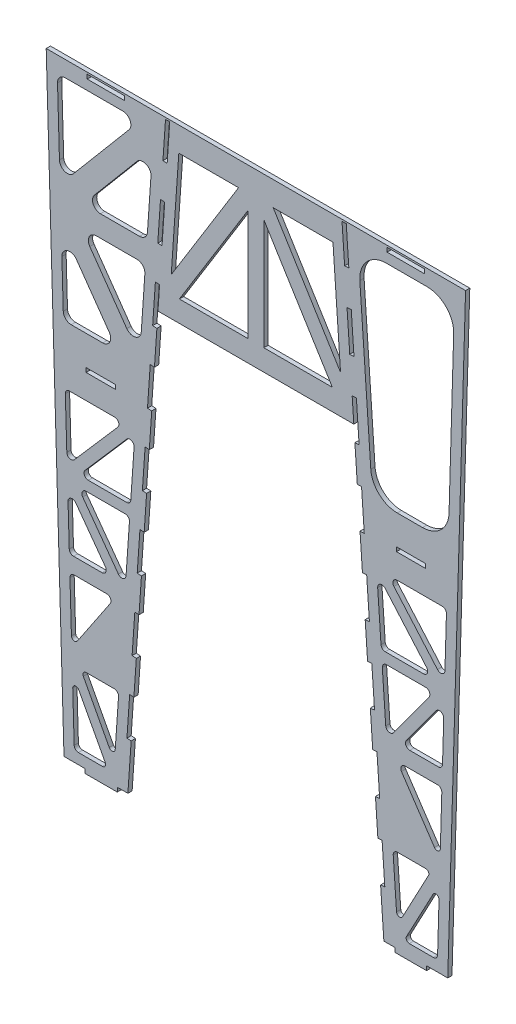
SolidWorks part; units mm, degrees
ref_plane "Front Plane" through (0, 0, 0) normal (0, 0, 1) x (1, 0, 0)
ref_plane "Top Plane" through (0, 0, 0) normal (0, 1, 0) x (1, 0, 0)
ref_plane "Right Plane" through (0, 0, 0) normal (1, 0, 0) x (0, 0, -1)
sketch "Sketch1" plane through (0, 0, 0) normal (0, 0, 1) x (1, 0, 0)
  line L0 (-288.2759, 0) -> (288.2759, 0) construction
  line L1 (-215.8925, 1465.1633) -> (215.8925, 1465.1633)
  line L2 (0, 0) -> (0, 1733.4513) construction
  line L3 (19.05, 1104.9) -> (205.6376, 1104.9)
  line L4 (202.8026, 1145.716) -> (41.4459, 1406.7433)
  line L5 (205.6376, 1104.9) -> (19.05, 1406.7433) construction
  line L6 (205.6376, 1104.9) -> (184.6725, 1406.7433)
  line L7 (183.2417, 1104.9) -> (15.2162, 1376.7154)
  line L8 (19.05, 1406.7433) -> (19.05, 1104.9)
  line L9 (184.6725, 1406.7433) -> (19.05, 1406.7433)
  line L10 (306.6278, 17.4764) -> (234.6272, 1054.1)
  line L12 (459.7218, 17.4764) -> (502.3797, 1465.1633)
  line L13 (459.4357, 7.4824) -> (519.9157, 2060.3987) construction
  line L15 (266.6925, 1465.1633) -> (368.5375, 1465.1633)
  line L16 (-237.2124, 1016.8799) -> (-230.6925, 1110.7494) construction
  line L18 (237.2124, 1016.8799) -> (230.6925, 1110.7494) construction
  line L19 (-408.9218, 7.3164) -> (-332.1008, 7.3164)
  line L20 (-502.3797, 1465.1633) -> (-215.8925, 1465.1633)
  line L22 (408.9218, 7.3164) -> (332.7218, 7.3164)
  line L24 (-408.9218, 17.4764) -> (-408.9218, 7.3164) construction
  line L30 (-408.9218, 17.4764) -> (-408.9218, 7.3164)
  line L31 (502.3797, 1465.1633) -> (368.5375, 1465.1633)
  line L32 (-332.1008, 17.4764) -> (-332.1008, 7.3164) construction
  line L33 (-332.1008, 17.4764) -> (-332.1008, 7.3164)
  line L34 (408.9218, 17.4764) -> (408.9218, 7.3164) construction
  line L35 (408.9218, 17.4764) -> (408.9218, 7.3164)
  line L40 (332.7218, 17.4764) -> (332.7218, 7.3164) construction
  line L43 (332.7218, 17.4764) -> (332.7218, 7.3164)
  line L44 (459.7218, 17.4764) -> (408.9218, 17.4764) construction
  line L45 (459.7218, 17.4764) -> (408.9218, 17.4764)
  line L49 (-408.9218, 17.4764) -> (-459.7218, 17.4764)
  line L52 (-332.1008, 17.4764) -> (-306.6278, 17.4764)
  line L53 (332.7218, 17.4764) -> (306.6278, 17.4764)
  line L55 (-459.7218, 17.4764) -> (-502.3797, 1465.1633)
  line L56 (-459.4357, 7.4824) -> (-519.9157, 2060.3987) construction
  line L81 (215.8925, 1465.1633) -> (266.6925, 1465.1633)
  line L90 (234.6272, 1054.1) -> (-234.6272, 1054.1)
  line L100 (-234.6272, 1054.1) -> (-306.6278, 17.4764)
  line L124 (-184.6725, 1406.7433) -> (-19.05, 1406.7433)
  line L125 (-19.05, 1406.7433) -> (-19.05, 1104.9)
  line L126 (-183.2417, 1104.9) -> (-15.2162, 1376.7154)
  line L127 (-205.6376, 1104.9) -> (-19.05, 1406.7433) construction
  line L128 (-202.8026, 1145.716) -> (-41.4459, 1406.7433)
  line L129 (-205.6376, 1104.9) -> (-184.6725, 1406.7433)
  line L130 (-19.05, 1104.9) -> (-205.6376, 1104.9)
  point P0 (0, 0)
  point P3 (0, 0)
  point P106 (0, 0)
  point P118 (0, 1054.1)
  dimension "D6" = 25.4
  dimension "D7" = 50.8
  dimension "D8" = 58.42
  dimension "D9" = 19.05
  dimension "D19" = 288.2759
  dimension "D22" = 19.05
  dimension "D23" = 19.05
  dimension "D24" = 1054.1
  dimension "D49" = 50.8
extrude "Boss-Extrude1" add sketch "Sketch1" along normal blind 10.16 contours L20 | L100 L90 L125 L130 L129 L124 | L100 | L130 L126 L125 L124 L128 L129 | L81 | L4 L9 L8 L7 L3 L6 | L15 region at (0, 1447.4578, 0) region at (111.9691, 1256.3298, 0) region at (-111.9691, 1256.3298, 0)
fillet "Fillet1" [suppressed] radius 19.05
sketch "Sketch2" plane through (0, 0, 0) normal (0, 0, 1) x (1, 0, 0)
  line L18 (-222.6942, 1372.2749) -> (-212.5765, 1371.5721) construction
  line L56 (-216.5353, 1460.9479) -> (-222.6942, 1372.2749) construction
  line L57 (-212.5765, 1371.5721) -> (-206.3688, 1460.9479) construction
  line L58 (-206.3688, 1460.9479) -> (-216.5353, 1460.9479) construction
  line L59 (-222.6942, 1372.2749) -> (-212.5765, 1371.5721)
  line L61 (-216.5353, 1460.9479) -> (-222.6942, 1372.2749)
  line L63 (-212.5765, 1371.5721) -> (-206.3688, 1460.9479)
  line L176 (-206.3688, 1460.9479) -> (-216.5353, 1460.9479)
  line L181 (-224.8945, 1194.226) -> (-235.0121, 1194.9287) construction
  line L194 (-224.8945, 1194.226) -> (-218.3727, 1288.1221) construction
  line L199 (-218.3727, 1288.1221) -> (-228.4904, 1288.8248) construction
  line L208 (-228.4904, 1288.8248) -> (-235.0121, 1194.9287) construction
  line L213 (-224.8945, 1194.226) -> (-235.0121, 1194.9287)
  line L330 (-224.8945, 1194.226) -> (-218.3727, 1288.1221)
  line L331 (-218.3727, 1288.1221) -> (-228.4904, 1288.8248)
  line L332 (-228.4904, 1288.8248) -> (-235.0121, 1194.9287)
  line L333 (224.8945, 1194.226) -> (235.0121, 1194.9287) construction
  line L334 (235.0121, 1194.9287) -> (228.4904, 1288.8248) construction
  line L335 (218.3727, 1288.1221) -> (224.8945, 1194.226) construction
  line L336 (228.4904, 1288.8248) -> (218.3727, 1288.1221) construction
  line L337 (212.5765, 1371.5721) -> (222.6942, 1372.2749) construction
  line L338 (206.3688, 1460.9479) -> (212.5765, 1371.5721) construction
  line L339 (216.5353, 1460.9479) -> (206.3688, 1460.9479) construction
  line L340 (222.6942, 1372.2749) -> (216.5353, 1460.9479) construction
  line L341 (224.8945, 1194.226) -> (235.0121, 1194.9287)
  line L342 (235.0121, 1194.9287) -> (228.4904, 1288.8248)
  line L343 (218.3727, 1288.1221) -> (224.8945, 1194.226)
  line L344 (228.4904, 1288.8248) -> (218.3727, 1288.1221)
  line L345 (212.5765, 1371.5721) -> (222.6942, 1372.2749)
  line L346 (206.3688, 1460.9479) -> (212.5765, 1371.5721)
  line L347 (216.5353, 1460.9479) -> (206.3688, 1460.9479)
  line L348 (222.6942, 1372.2749) -> (216.5353, 1460.9479)
  line L349 (-240.8102, 1111.4521) -> (-247.33, 1017.5826) construction
  line L350 (-247.33, 1017.5826) -> (-237.2124, 1016.8799) construction
  line L351 (-230.6925, 1110.7494) -> (-240.8102, 1111.4521) construction
  line L353 (-240.8102, 1111.4521) -> (-247.33, 1017.5826)
  line L354 (-247.33, 1017.5826) -> (-237.2124, 1016.8799)
  line L355 (-230.6925, 1110.7494) -> (-240.8102, 1111.4521)
  line L357 (237.2124, 1016.8799) -> (247.33, 1017.5826) construction
  line L358 (247.33, 1017.5826) -> (240.8102, 1111.4521) construction
  line L360 (240.8102, 1111.4521) -> (230.6925, 1110.7494) construction
  line L361 (237.2124, 1016.8799) -> (247.33, 1017.5826)
  line L362 (247.33, 1017.5826) -> (240.8102, 1111.4521)
  line L364 (240.8102, 1111.4521) -> (230.6925, 1110.7494)
  line L365 (-306.6278, 17.4764) -> (-234.6272, 1054.1)
  line L366 (-234.6272, 1054.1) -> (234.6272, 1054.1)
  line L367 (234.6272, 1054.1) -> (306.6278, 17.4764)
  line L372 (408.9218, 17.4764) -> (459.7218, 17.4764)
  line L373 (459.7218, 17.4764) -> (502.3797, 1465.1633)
  line L374 (502.3797, 1465.1633) -> (-502.3797, 1465.1633)
  line L375 (-502.3797, 1465.1633) -> (-459.7218, 17.4764)
  line L376 (-459.7218, 17.4764) -> (-408.9218, 17.4764)
  line L377 (-408.9218, 17.4764) -> (-408.9218, 7.3164)
  line L378 (-408.9218, 7.3164) -> (-332.1008, 7.3164)
  line L379 (-332.1008, 7.3164) -> (-332.1008, 17.4764)
  line L380 (-332.1008, 17.4764) -> (-306.6278, 17.4764)
  line L381 (-298.8019, 130.1492) -> (-292.2913, 223.886)
  line L405 (-243.0122, 933.3767) -> (-253.1299, 934.0795) construction
  line L406 (-253.1299, 934.0795) -> (-259.648, 840.2365) construction
  line L407 (-249.5303, 839.5337) -> (-259.648, 840.2365) construction
  line L408 (-243.0122, 933.3767) -> (-253.1299, 934.0795)
  line L417 (-253.1299, 934.0795) -> (-259.648, 840.2365)
  line L418 (-249.5303, 839.5337) -> (-259.648, 840.2365)
  line L419 (243.0122, 933.3767) -> (253.1299, 934.0795) construction
  line L420 (253.1299, 934.0795) -> (259.648, 840.2365) construction
  line L421 (249.5303, 839.5337) -> (259.648, 840.2365) construction
  line L422 (243.0122, 933.3767) -> (253.1299, 934.0795)
  line L423 (253.1299, 934.0795) -> (259.648, 840.2365)
  line L424 (249.5303, 839.5337) -> (259.648, 840.2365)
  line L425 (-267.6517, 578.6314) -> (-277.7694, 579.3341) construction
  line L426 (-255.332, 756.0041) -> (-265.4497, 756.7068) construction
  line L427 (-265.4497, 756.7068) -> (-271.9659, 662.8903) construction
  line L428 (-261.8482, 662.1876) -> (-271.9659, 662.8903) construction
  line L429 (-277.7694, 579.3341) -> (-284.2838, 485.5442) construction
  line L430 (-274.1661, 484.8415) -> (-284.2838, 485.5442) construction
  line L431 (-274.1661, 484.8415) -> (-284.2838, 485.5442)
  line L432 (-277.7694, 579.3341) -> (-284.2838, 485.5442)
  line L433 (-267.6517, 578.6314) -> (-277.7694, 579.3341)
  line L434 (-261.8482, 662.1876) -> (-271.9659, 662.8903)
  line L435 (-265.4497, 756.7068) -> (-271.9659, 662.8903)
  line L436 (-255.332, 756.0041) -> (-265.4497, 756.7068)
  line L437 (261.8482, 662.1876) -> (271.9659, 662.8903) construction
  line L438 (255.332, 756.0041) -> (265.4497, 756.7068) construction
  line L439 (265.4497, 756.7068) -> (271.9659, 662.8903) construction
  line L440 (261.8482, 662.1876) -> (271.9659, 662.8903)
  line L449 (255.332, 756.0041) -> (265.4497, 756.7068)
  line L450 (265.4497, 756.7068) -> (271.9659, 662.8903)
  line L451 (274.1661, 484.8415) -> (284.2838, 485.5442) construction
  line L452 (277.7694, 579.3341) -> (284.2838, 485.5442) construction
  line L453 (267.6517, 578.6314) -> (277.7694, 579.3341) construction
  line L454 (274.1661, 484.8415) -> (284.2838, 485.5442)
  line L455 (277.7694, 579.3341) -> (284.2838, 485.5442)
  line L456 (267.6517, 578.6314) -> (277.7694, 579.3341)
  line L457 (-298.8019, 130.1492) -> (-308.9196, 130.8519) construction
  line L458 (-302.4089, 224.5888) -> (-308.9196, 130.8519) construction
  line L459 (-292.2913, 223.886) -> (-302.4089, 224.5888) construction
  line L460 (-286.484, 307.4953) -> (-296.6017, 308.1981) construction
  line L461 (-290.0892, 401.9615) -> (-296.6017, 308.1981) construction
  line L462 (-279.9715, 401.2587) -> (-290.0892, 401.9615) construction
  line L463 (-298.8019, 130.1492) -> (-308.9196, 130.8519)
  line L464 (-302.4089, 224.5888) -> (-308.9196, 130.8519)
  line L465 (-292.2913, 223.886) -> (-302.4089, 224.5888)
  line L466 (-286.484, 307.4953) -> (-296.6017, 308.1981)
  line L467 (-290.0892, 401.9615) -> (-296.6017, 308.1981)
  line L468 (-279.9715, 401.2587) -> (-290.0892, 401.9615)
  line L469 (286.484, 307.4953) -> (296.6017, 308.1981) construction
  line L470 (279.9715, 401.2587) -> (290.0892, 401.9615) construction
  line L471 (290.0892, 401.9615) -> (296.6017, 308.1981) construction
  line L472 (286.484, 307.4953) -> (296.6017, 308.1981)
  line L473 (279.9715, 401.2587) -> (290.0892, 401.9615)
  line L474 (290.0892, 401.9615) -> (296.6017, 308.1981)
  line L475 (298.8019, 130.1492) -> (308.9196, 130.8519) construction
  line L476 (302.4089, 224.5888) -> (308.9196, 130.8519) construction
  line L477 (292.2913, 223.886) -> (302.4089, 224.5888) construction
  line L478 (298.8019, 130.1492) -> (308.9196, 130.8519)
  line L479 (302.4089, 224.5888) -> (308.9196, 130.8519)
  line L480 (292.2913, 223.886) -> (302.4089, 224.5888)
  line L481 (-230.6925, 1110.7494) -> (-237.2124, 1016.8799)
  line L482 (243.0122, 933.3767) -> (249.5303, 839.5337)
  line L483 (255.332, 756.0041) -> (261.8482, 662.1876)
  line L484 (-249.5303, 839.5337) -> (-243.0122, 933.3767)
  line L485 (-261.8482, 662.1876) -> (-255.332, 756.0041)
  line L486 (267.6517, 578.6314) -> (274.1661, 484.8415)
  line L487 (-286.484, 307.4953) -> (-279.9715, 401.2587)
  line L488 (-274.1661, 484.8415) -> (-267.6517, 578.6314)
  line L489 (279.9715, 401.2587) -> (286.484, 307.4953)
  line L490 (292.2913, 223.886) -> (298.8019, 130.1492)
  line L492 (230.6925, 1110.7494) -> (237.2124, 1016.8799)
  line L499 (306.6278, 17.4764) -> (332.7218, 17.4764)
  line L500 (332.7218, 17.4764) -> (332.7218, 7.3164)
  line L501 (332.7218, 7.3164) -> (408.9218, 7.3164)
  line L502 (408.9218, 7.3164) -> (408.9218, 17.4764)
  dimension "D1" = 0
extrude "Cut-Extrude5" cut sketch "Sketch2" along normal blind 12.7
sketch "Sketch4" plane through (0, 0, 10.16) normal (0, 0, 1) x (1, 0, 0)
  line L0 (404.2136, 1450.7879) -> (404.2136, 1460.9479) construction
  line L1 (314.2136, 1450.7879) -> (404.2136, 1450.7879) construction
  line L2 (314.2136, 1450.7879) -> (314.2136, 1460.9479) construction
  line L3 (404.2136, 1460.9479) -> (314.2136, 1460.9479) construction
  line L4 (404.2136, 1450.7879) -> (404.2136, 1460.9479)
  line L5 (314.2136, 1450.7879) -> (404.2136, 1450.7879)
  line L6 (314.2136, 1450.7879) -> (314.2136, 1460.9479)
  line L7 (404.2136, 1460.9479) -> (314.2136, 1460.9479)
  line L8 (336.7821, 840.6279) -> (336.7821, 850.7879) construction
  line L9 (336.7821, 840.6279) -> (406.7821, 840.6279) construction
  line L10 (406.7821, 840.6279) -> (406.7821, 850.7879) construction
  line L11 (406.7821, 850.7879) -> (336.7821, 850.7879) construction
  line L12 (336.7821, 840.6279) -> (336.7821, 850.7879)
  line L13 (336.7821, 840.6279) -> (406.7821, 840.6279)
  line L14 (406.7821, 840.6279) -> (406.7821, 850.7879)
  line L15 (406.7821, 850.7879) -> (336.7821, 850.7879)
extrude "Cut-Extrude6" cut sketch "Sketch4" against normal through all both
ref_plane "Plane1" through (0, 0, 0) normal (1, 0, 0) x (0, 0, -1)
mirror "Mirror1" about plane through (0, 0, 0) normal (1, 0, 0) of "Cut-Extrude6"
sketch "Sketch5" plane through (0, 0, 10.16) normal (0, 0, 1) x (1, 0, 0)
  line L0 (435.0592, 42.8764) -> (475.846, 1427.0633)
  line L1 (475.846, 1427.0633) -> (244.35, 1427.0633)
  line L2 (244.35, 1427.0633) -> (340.4913, 42.8764)
  line L3 (340.4913, 42.8764) -> (435.0592, 42.8764)
  line L4 (281.2007, 896.5079) -> (460.2126, 896.5079)
  line L5 (457.2188, 794.9079) -> (288.2575, 794.9079)
  line L6 (336.7821, 840.6279) -> (406.7821, 840.6279) construction
  line L7 (475.846, 1427.0633) -> (460.2126, 896.5079)
  line L8 (468.0293, 1161.7856) -> (281.2007, 896.5079) construction
  line L9 (244.35, 1427.0633) -> (468.0293, 1161.7856) construction
  line L10 (244.35, 1427.0633) -> (281.2007, 896.5079)
  line L11 (281.2007, 896.5079) -> (244.35, 1427.0633)
  line L12 (262.7753, 1161.7856) -> (468.0293, 1161.7856) construction
  line L13 (435.0592, 42.8764) -> (457.2188, 794.9079)
  line L14 (446.139, 418.8922) -> (457.2188, 794.9079)
  line L15 (451.6789, 606.9001) -> (288.2575, 794.9079) construction
  line L16 (451.6789, 606.9001) -> (314.3744, 418.8922) construction
  line L17 (446.139, 418.8922) -> (435.0592, 42.8764)
  line L18 (440.5991, 230.8843) -> (314.3744, 418.8922) construction
  line L19 (440.5991, 230.8843) -> (340.4913, 42.8764) construction
  line L20 (451.6789, 606.9001) -> (301.316, 606.9001) construction
  line L21 (314.3744, 418.8922) -> (446.139, 418.8922) construction
  line L22 (440.5991, 230.8843) -> (327.4329, 230.8843) construction
  line L23 (354.8795, 42.8764) -> (439.7562, 202.2796)
  line L24 (338.831, 66.78) -> (419.4486, 218.1843)
  line L25 (328.315, 218.1843) -> (419.4486, 218.1843)
  line L26 (326.5508, 243.5843) -> (416.7758, 243.5843)
  line L27 (416.7758, 243.5843) -> (316.1395, 393.479)
  line L28 (441.2422, 252.7104) -> (338.1977, 406.1922)
  line L29 (338.1977, 406.1922) -> (445.7648, 406.1922)
  line L30 (446.8874, 444.2922) -> (348.6506, 444.2922)
  line L31 (348.6506, 444.2922) -> (451.0177, 584.4611)
  line L32 (313.0087, 438.5556) -> (426.6777, 594.2001)
  line L33 (426.6777, 594.2001) -> (302.1981, 594.2001)
  line L34 (300.4339, 619.6001) -> (423.8126, 619.6001)
  line L35 (423.8126, 619.6001) -> (289.7189, 773.8679)
  line L36 (452.2306, 625.6241) -> (316.1239, 782.2079)
  line L37 (316.1239, 782.2079) -> (456.8446, 782.2079)
  line L38 (277.5742, 1427.0633) -> (469.1512, 1199.8582)
  line L39 (247.3325, 1384.1232) -> (413.3881, 1187.1856)
  line L40 (413.3881, 1187.1856) -> (261.0111, 1187.1856)
  line L41 (264.5396, 1136.3856) -> (419.0736, 1136.3856)
  line L42 (419.0736, 1136.3856) -> (278.4119, 936.6601)
  line L43 (466.6727, 1115.7474) -> (330.1564, 921.9079)
  line L44 (330.1564, 921.9079) -> (460.961, 921.9079)
  line L64 (-234.6272, 1054.1) -> (234.6272, 1054.1)
  line L65 (234.6272, 1054.1) -> (230.6925, 1110.7494)
  line L66 (230.6925, 1110.7494) -> (240.8102, 1111.4521)
  line L67 (240.8102, 1111.4521) -> (247.33, 1017.5826)
  line L68 (247.33, 1017.5826) -> (237.2124, 1016.8799)
  line L69 (237.2124, 1016.8799) -> (243.0122, 933.3767)
  line L70 (243.0122, 933.3767) -> (253.1299, 934.0795)
  line L71 (253.1299, 934.0795) -> (259.648, 840.2365)
  line L72 (259.648, 840.2365) -> (249.5303, 839.5337)
  line L73 (249.5303, 839.5337) -> (255.332, 756.0041)
  line L74 (255.332, 756.0041) -> (265.4497, 756.7068)
  line L75 (265.4497, 756.7068) -> (271.9659, 662.8903)
  line L76 (271.9659, 662.8903) -> (261.8482, 662.1876)
  line L77 (261.8482, 662.1876) -> (267.6517, 578.6314)
  line L78 (267.6517, 578.6314) -> (277.7694, 579.3341)
  line L79 (277.7694, 579.3341) -> (284.2838, 485.5442)
  line L80 (284.2838, 485.5442) -> (274.1661, 484.8415)
  line L81 (274.1661, 484.8415) -> (279.9715, 401.2587)
  line L82 (279.9715, 401.2587) -> (290.0892, 401.9615)
  line L83 (290.0892, 401.9615) -> (296.6017, 308.1981)
  line L84 (296.6017, 308.1981) -> (286.484, 307.4953)
  line L85 (286.484, 307.4953) -> (292.2913, 223.886)
  line L86 (292.2913, 223.886) -> (302.4089, 224.5888)
  line L87 (302.4089, 224.5888) -> (308.9196, 130.8519)
  line L88 (308.9196, 130.8519) -> (298.8019, 130.1492)
  line L89 (298.8019, 130.1492) -> (306.6278, 17.4764)
  line L90 (306.6278, 17.4764) -> (332.7218, 17.4764)
  line L91 (332.7218, 17.4764) -> (332.7218, 7.3164)
  line L92 (332.7218, 7.3164) -> (408.9218, 7.3164)
  line L93 (408.9218, 7.3164) -> (408.9218, 17.4764)
  line L94 (408.9218, 17.4764) -> (459.7218, 17.4764)
  line L95 (459.7218, 17.4764) -> (502.3797, 1465.1633)
  line L96 (502.3797, 1465.1633) -> (-502.3797, 1465.1633)
  line L97 (-502.3797, 1465.1633) -> (-459.7218, 17.4764)
  line L98 (-459.7218, 17.4764) -> (-408.9218, 17.4764)
  line L99 (-408.9218, 17.4764) -> (-408.9218, 7.3164)
  line L100 (-408.9218, 7.3164) -> (-332.1008, 7.3164)
  line L101 (-332.1008, 7.3164) -> (-332.1008, 17.4764)
  line L102 (-332.1008, 17.4764) -> (-306.6278, 17.4764)
  line L103 (-306.6278, 17.4764) -> (-298.8019, 130.1492)
  line L104 (-298.8019, 130.1492) -> (-308.9196, 130.8519)
  line L105 (-308.9196, 130.8519) -> (-302.4089, 224.5888)
  line L106 (-302.4089, 224.5888) -> (-292.2913, 223.886)
  line L107 (-292.2913, 223.886) -> (-286.484, 307.4953)
  line L108 (-286.484, 307.4953) -> (-296.6017, 308.1981)
  line L109 (-296.6017, 308.1981) -> (-290.0892, 401.9615)
  line L110 (-290.0892, 401.9615) -> (-279.9715, 401.2587)
  line L111 (-279.9715, 401.2587) -> (-274.1661, 484.8415)
  line L112 (-274.1661, 484.8415) -> (-284.2838, 485.5442)
  line L113 (-284.2838, 485.5442) -> (-277.7694, 579.3341)
  line L114 (-277.7694, 579.3341) -> (-267.6517, 578.6314)
  line L115 (-267.6517, 578.6314) -> (-261.8482, 662.1876)
  line L116 (-261.8482, 662.1876) -> (-271.9659, 662.8903)
  line L117 (-271.9659, 662.8903) -> (-265.4497, 756.7068)
  line L118 (-265.4497, 756.7068) -> (-255.332, 756.0041)
  line L119 (-255.332, 756.0041) -> (-249.5303, 839.5337)
  line L120 (-249.5303, 839.5337) -> (-259.648, 840.2365)
  line L121 (-259.648, 840.2365) -> (-253.1299, 934.0795)
  line L122 (-253.1299, 934.0795) -> (-243.0122, 933.3767)
  line L123 (-243.0122, 933.3767) -> (-237.2124, 1016.8799)
  line L124 (-237.2124, 1016.8799) -> (-247.33, 1017.5826)
  line L125 (-247.33, 1017.5826) -> (-240.8102, 1111.4521)
  line L126 (-240.8102, 1111.4521) -> (-230.6925, 1110.7494)
  line L127 (-230.6925, 1110.7494) -> (-234.6272, 1054.1)
  line L128 (-234.6272, 1054.1) -> (234.6272, 1054.1)
  line L129 (234.6272, 1054.1) -> (230.6925, 1110.7494)
  line L130 (230.6925, 1110.7494) -> (240.8102, 1111.4521)
  line L131 (240.8102, 1111.4521) -> (247.33, 1017.5826)
  line L132 (247.33, 1017.5826) -> (237.2124, 1016.8799)
  line L133 (237.2124, 1016.8799) -> (243.0122, 933.3767)
  line L134 (243.0122, 933.3767) -> (253.1299, 934.0795)
  line L135 (253.1299, 934.0795) -> (259.648, 840.2365)
  line L136 (259.648, 840.2365) -> (249.5303, 839.5337)
  line L137 (249.5303, 839.5337) -> (255.332, 756.0041)
  line L138 (255.332, 756.0041) -> (265.4497, 756.7068)
  line L139 (265.4497, 756.7068) -> (271.9659, 662.8903)
  line L140 (271.9659, 662.8903) -> (261.8482, 662.1876)
  line L141 (261.8482, 662.1876) -> (267.6517, 578.6314)
  line L142 (267.6517, 578.6314) -> (277.7694, 579.3341)
  line L143 (277.7694, 579.3341) -> (284.2838, 485.5442)
  line L144 (284.2838, 485.5442) -> (274.1661, 484.8415)
  line L145 (274.1661, 484.8415) -> (279.9715, 401.2587)
  line L146 (279.9715, 401.2587) -> (290.0892, 401.9615)
  line L147 (290.0892, 401.9615) -> (296.6017, 308.1981)
  line L148 (296.6017, 308.1981) -> (286.484, 307.4953)
  line L149 (286.484, 307.4953) -> (292.2913, 223.886)
  line L150 (292.2913, 223.886) -> (302.4089, 224.5888)
  line L151 (302.4089, 224.5888) -> (308.9196, 130.8519)
  line L152 (308.9196, 130.8519) -> (298.8019, 130.1492)
  line L153 (298.8019, 130.1492) -> (306.6278, 17.4764)
  line L154 (306.6278, 17.4764) -> (332.7218, 17.4764)
  line L155 (332.7218, 17.4764) -> (332.7218, 7.3164)
  line L156 (332.7218, 7.3164) -> (408.9218, 7.3164)
  line L157 (408.9218, 7.3164) -> (408.9218, 17.4764)
  line L158 (408.9218, 17.4764) -> (459.7218, 17.4764)
  line L159 (459.7218, 17.4764) -> (502.3797, 1465.1633)
  line L160 (502.3797, 1465.1633) -> (-502.3797, 1465.1633)
  line L161 (-502.3797, 1465.1633) -> (-459.7218, 17.4764)
  line L162 (-459.7218, 17.4764) -> (-408.9218, 17.4764)
  line L163 (-408.9218, 17.4764) -> (-408.9218, 7.3164)
  line L164 (-408.9218, 7.3164) -> (-332.1008, 7.3164)
  line L165 (-332.1008, 7.3164) -> (-332.1008, 17.4764)
  line L166 (-332.1008, 17.4764) -> (-306.6278, 17.4764)
  line L167 (-306.6278, 17.4764) -> (-298.8019, 130.1492)
  line L168 (-298.8019, 130.1492) -> (-308.9196, 130.8519)
  line L169 (-308.9196, 130.8519) -> (-302.4089, 224.5888)
  line L170 (-302.4089, 224.5888) -> (-292.2913, 223.886)
  line L171 (-292.2913, 223.886) -> (-286.484, 307.4953)
  line L172 (-286.484, 307.4953) -> (-296.6017, 308.1981)
  line L173 (-296.6017, 308.1981) -> (-290.0892, 401.9615)
  line L174 (-290.0892, 401.9615) -> (-279.9715, 401.2587)
  line L175 (-279.9715, 401.2587) -> (-274.1661, 484.8415)
  line L176 (-274.1661, 484.8415) -> (-284.2838, 485.5442)
  line L177 (-284.2838, 485.5442) -> (-277.7694, 579.3341)
  line L178 (-277.7694, 579.3341) -> (-267.6517, 578.6314)
  line L179 (-267.6517, 578.6314) -> (-261.8482, 662.1876)
  line L180 (-261.8482, 662.1876) -> (-271.9659, 662.8903)
  line L181 (-271.9659, 662.8903) -> (-265.4497, 756.7068)
  line L182 (-265.4497, 756.7068) -> (-255.332, 756.0041)
  line L183 (-255.332, 756.0041) -> (-249.5303, 839.5337)
  line L184 (-249.5303, 839.5337) -> (-259.648, 840.2365)
  line L185 (-259.648, 840.2365) -> (-253.1299, 934.0795)
  line L186 (-253.1299, 934.0795) -> (-243.0122, 933.3767)
  line L187 (-243.0122, 933.3767) -> (-237.2124, 1016.8799)
  line L188 (-237.2124, 1016.8799) -> (-247.33, 1017.5826)
  line L189 (-247.33, 1017.5826) -> (-240.8102, 1111.4521)
  line L190 (-240.8102, 1111.4521) -> (-230.6925, 1110.7494)
  line L191 (-230.6925, 1110.7494) -> (-234.6272, 1054.1)
  dimension "D2" = 38.1
  dimension "D3" = 25.4
  dimension "D4" = 25.4
  dimension "D5" = 25.4
  dimension "D6" = 101.6
  dimension "D7" = 45.72
  dimension "D8" = 12.7
  dimension "D9" = 12.7
  dimension "D10" = 12.7
  dimension "D11" = 12.7
  dimension "D12" = 12.7
  dimension "D13" = 12.7
  dimension "D14" = 12.7
  dimension "D15" = 25.4
  dimension "D16" = 12.7
  dimension "D17" = 12.7
  dimension "D18" = 12.7
  dimension "D19" = 12.7
  dimension "D20" = 12.7
  dimension "D21" = 12.7
  dimension "D22" = 12.7
  dimension "D23" = 25.4
  dimension "D24" = 25.4
  dimension "D25" = 25.4
  dimension "D26" = 25.4
  dimension "D27" = 25.4
  dimension "D28" = 25.4
  dimension "D29" = 25.4
  dimension "D1" = 0
extrude "Cut-Extrude7" cut sketch "Sketch5" against normal through all both contours L1 L38 L7 | L40 L39 L11 | L42 L41 L11 | L43 L44 L7 | L37 L36 L14 | L34 L35 L2 | L32 L33 L2 | L31 L30 L14 | L29 L28 L0 | L26 L27 L2 | L25 L2 L24 | L23 L3 L0 region at (409.8983, 96.0108, 10.16) region at (408.4016, 355.0316, 10.16) region at (362.1982, 167.7162, 10.16) region at (415.5186, 491.0151, 10.16) region at (353.1554, 293.5492, 10.16) region at (408.3997, 730.0133, 10.16) region at (347.2948, 542.3186, 10.16) region at (337.9884, 671.0227, 10.16) region at (419.2634, 986.5211, 10.16) region at (320.675, 1069.8105, 10.16) region at (407.5238, 1351.3283, 10.16) region at (307.2439, 1252.8315, 10.16)
fillet "Fillet3" radius 10.16 18 edges at (446.8874, 444.2922, 5.08) (416.7758, 243.5843, 5.08) (338.1977, 406.1922, 5.08) (348.6506, 444.2922, 5.08) (445.7648, 406.1922, 5.08) (326.5508, 243.5843, 5.08) (313.0087, 438.5556, 5.08) (451.0177, 584.4611, 5.08) (426.6777, 594.2001, 5.08) (302.1981, 594.2001, 5.08) (300.4339, 619.6001, 5.08) (423.8126, 619.6001, 5.08) (452.2306, 625.6241, 5.08) (289.7189, 773.8679, 5.08) (316.1239, 782.2079, 5.08) (456.8446, 782.2079, 5.08) (435.0592, 42.8764, 5.08) (328.315, 218.1843, 5.08)
fillet "Fillet4" radius 7.62 6 edges at (354.8795, 42.8764, 5.08) (419.4486, 218.1843, 5.08) (316.1395, 393.479, 5.08) (439.7562, 202.2796, 5.08) (338.831, 66.78, 5.08) (441.2422, 252.7104, 5.08)
fillet "Fillet5" radius 19.05 12 edges at (330.1564, 921.9079, 5.08) (460.961, 921.9079, 5.08) (419.0736, 1136.3856, 5.08) (466.6727, 1115.7474, 5.08) (475.846, 1427.0633, 5.08) (469.1512, 1199.8582, 5.08) (413.3881, 1187.1856, 5.08) (277.5742, 1427.0633, 5.08) (247.3325, 1384.1232, 5.08) (264.5396, 1136.3856, 5.08) (261.0111, 1187.1856, 5.08) (278.4119, 936.6601, 5.08)
mirror "Mirror2" about plane through (0, 0, 0) normal (1, 0, 0) of "Cut-Extrude7", "Fillet3", "Fillet4", "Fillet5"
sketch "Sketch6" plane through (0, 0, 10.16) normal (0, 0, 1) x (1, 0, 0)
  line L0 (244.35, 1427.0633) -> (279.4365, 921.9079)
  line L1 (279.4365, 921.9079) -> (460.961, 921.9079)
  line L2 (460.961, 921.9079) -> (475.846, 1427.0633)
  line L3 (366.8731, 921.9079) -> (442.4641, 921.9079) construction
  line L4 (244.35, 1427.0633) -> (475.846, 1427.0633)
  line L5 (470.6195, 1249.6909) -> (475.2682, 1407.4522) construction
  line L6 (251.3752, 1325.9178) -> (259.7797, 1204.9157) construction
  line L7 (456.2264, 1427.0633) -> (318.5551, 1427.0633) construction
extrude "Cut-Extrude8" cut sketch "Sketch6" against normal through all both
fillet "Fillet6" radius 63.5 4 edges at (475.846, 1427.0633, 5.08) (460.961, 921.9079, 5.08) (279.4365, 921.9079, 5.08) (244.35, 1427.0633, 5.08)
sketch "Sketch7" plane through (0, 0, 10.16) normal (0, 0, 1) x (1, 0, 0)
  line L0 (-336.0296, 243.5843) -> (-397.7172, 243.5843) construction
  line L1 (-318.1167, 365.0131) -> (-325.894, 253.0403) construction
  line L2 (-406.1524, 259.4075) -> (-332.0448, 369.7885) construction
  line L3 (-336.0296, 243.5843) -> (-397.7172, 243.5843)
  line L4 (-318.1167, 365.0131) -> (-325.894, 253.0403)
  line L5 (-406.1524, 259.4075) -> (-332.0448, 369.7885)
  arc A0 (-406.1524, 259.4075) -> (-397.7172, 243.5843) centre (-397.7172, 253.7443) ccw construction
  arc A1 (-336.0296, 243.5843) -> (-325.894, 253.0403) centre (-336.0296, 253.7443) ccw construction
  arc A2 (-318.1167, 365.0131) -> (-332.0448, 369.7885) centre (-325.7184, 365.5411) ccw construction
  arc A3 (-406.1524, 259.4075) -> (-397.7172, 243.5843) centre (-397.7172, 253.7443) ccw
  arc A4 (-336.0296, 243.5843) -> (-325.894, 253.0403) centre (-336.0296, 253.7443) ccw
  arc A5 (-318.1167, 365.0131) -> (-332.0448, 369.7885) centre (-325.7184, 365.5411) ccw
extrude "Boss-Extrude2" add sketch "Sketch7" against normal up to surface (10.16 mm away) contours A3 L3 A4 L4 A5 L5 up to face at (-346.4743, 545.9059, 0)
mirror "Mirror3" about plane through (0, 0, 0) normal (1, 0, 0) of "Boss-Extrude2"
